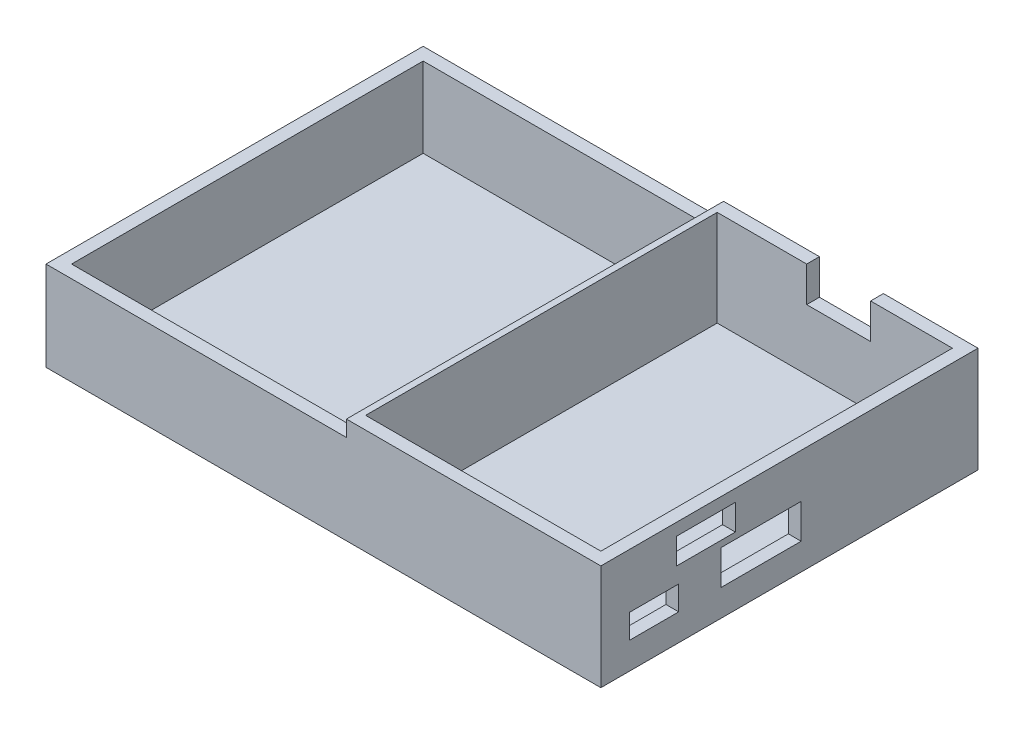
SolidWorks part; units mm, degrees
ref_plane "Front Plane" through (0, 0, 0) normal (0, 0, 1) x (1, 0, 0)
ref_plane "Top Plane" through (0, 0, 0) normal (0, 1, 0) x (1, 0, 0)
ref_plane "Right Plane" through (0, 0, 0) normal (1, 0, 0) x (0, 0, -1)
sketch "Sketch1" plane through (0, 0, 0) normal (0, 1, 0) x (1, 0, 0)
  line L1 (22.5, -27.5) -> (-22.5, -27.5)
  line L2 (22.5, -27.5) -> (22.5, 27.5)
  line L3 (22.5, 27.5) -> (-22.5, 27.5)
  line L4 (-22.5, -27.5) -> (-22.5, 27.5)
  line L5 (22.5, -27.5) -> (-22.5, 27.5) construction
  line L6 (22.5, 27.5) -> (-22.5, -27.5) construction
  line L10 (23.5, 27.5) -> (23.5, -27.5)
  line L11 (23.5, 27.5) -> (60.3, 27.5)
  line L12 (23.5, -27.5) -> (60.3, -27.5)
  line L13 (60.3, 27.5) -> (60.3, -27.5)
  line L14 (22.5, 27.5) -> (22.5, -27.5)
  line L15 (22.5, 27.5) -> (23.5, 27.5)
  line L16 (22.5, -27.5) -> (23.5, -27.5)
  line L17 (23.5, 27.5) -> (23.5, -27.5)
  line L18 (22.5, -29.5) -> (-24.5, -29.5)
  line L19 (-24.5, -29.5) -> (-24.5, 29.5)
  line L20 (22.5, 29.5) -> (-24.5, 29.5)
  line L21 (22.5, 29.5) -> (23.5, 29.5)
  line L22 (23.5, 29.5) -> (62.3, 29.5)
  line L23 (62.3, 29.5) -> (62.3, -29.5)
  line L24 (23.5, -29.5) -> (62.3, -29.5)
  line L25 (22.5, -29.5) -> (23.5, -29.5)
  line L26 (22.5, 29.5) -> (22.5, 27.5)
  line L27 (22.5, -27.5) -> (22.5, -29.5)
  line L29 (22.5, 27.5) -> (23.5, 27.5)
  line L30 (22.5, 27.5) -> (22.5, -27.5)
  line L31 (22.5, -27.5) -> (23.5, -27.5)
  line L32 (23.5, 27.5) -> (23.5, -27.5)
  point P0 (0, 0)
  point P18 (-62.1185, 18.7953)
  dimension "D1" = 55
  dimension "D2" = 45
  dimension "D3" = 1
  dimension "D4" = 2
  dimension "D5" = 86.8
  dimension "D6" = 36.8
  dimension "D7" = 59
extrude "Boss-Extrude1" add sketch "Sketch1" along normal blind 12.5 contours L27 L1 L4 L3 L26 L20 L19 L18 region at (21.7457, 0, 28.5)
extrude "Boss-Extrude2" add sketch "Sketch1<5>" along normal blind 15 contours L16 L27 L25 L24 L23 L22 L21 L26 L15 L11 L13 L12 region at (23, 0, 28.2117)
sketch "Sketch1<5>" plane through (0, 0, 0) normal (0, 1, 0) x (1, 0, 0) same geometry as "Sketch1"
extrude "Boss-Extrude3" add sketch "Sketch1<7>" along normal blind 15 contours L2 L16 L10 L15 region at (23, 0, 0)
sketch "Sketch1<7>" plane through (0, 0, 0) normal (0, 1, 0) x (1, 0, 0) same geometry as "Sketch1"
extrude "Boss-Extrude5" add sketch "Sketch1<10>" against normal blind 1.5 contours L27 L1 L4 L3 L26 L20 L19 L18 | L4 L1 L2 L3 | L13 L11 L10 L12 | L2 L16 L10 L15 | L16 L27 L25 L24 L23 L22 L21 L26 L15 L11 L13 L12 region at (21.7457, 0, 28.5) region at (0, 0, 0) region at (23, 0, 0) region at (23, 0, 28.2117) region at (41.9, 0, 0)
sketch "Sketch1<10>" plane through (0, 0, 0) normal (0, 1, 0) x (1, 0, 0) same geometry as "Sketch1"
sketch "Sketch2" plane through (62.3, 0, 0) normal (1, 0, 0) x (0, 0, -1)
  line L0 (-25, 2.6848) -> (-17.3172, 2.6848)
  line L1 (-25, 2.6848) -> (-25, 6.4701)
  line L2 (-25, 6.4701) -> (-17.3172, 6.4701)
  line L3 (-17.3172, 2.6848) -> (-17.3172, 6.4701)
  line L4 (-10.6702, 2.6801) -> (-10.6702, 8.0801)
  line L5 (-10.6702, 8.0801) -> (1.8298, 8.0801)
  line L6 (1.8298, 2.6801) -> (1.8298, 8.0801)
  line L7 (-10.6702, 2.6801) -> (1.8298, 2.6801)
  line L8 (-17.6602, 9.0683) -> (-8.4602, 9.0683)
  line L9 (-17.6602, 9.0683) -> (-17.6602, 13.1)
  line L10 (-17.6602, 13.1) -> (-8.4602, 13.1)
  line L11 (-8.4602, 9.0683) -> (-8.4602, 13.1)
  line L12 (-29.5, 15) -> (-29.5, -1.5) construction
  line L13 (29.5, 15) -> (-29.5, 15) construction
  dimension "D1" = 0.9882
  dimension "D2" = 2.5982
  dimension "D3" = 9.2
  dimension "D4" = 2.21
  dimension "D5" = 0.343
  dimension "D6" = 4.5
  dimension "D7" = 1.9
  dimension "D8" = 4.0317
extrude "Cut-Extrude1" cut sketch "Sketch2" against normal blind 10
sketch "Sketch3" plane through (0, 0, -29.5) normal (0, 0, -1) x (-1, 0, 0)
  line L0 (-22.5, 15) -> (-22.5, 12.5) construction
  line L1 (-47.5, 15) -> (-37.5, 15)
  line L2 (-47.5, 15) -> (-47.5, 9.5)
  line L3 (-47.5, 9.5) -> (-37.5, 9.5)
  line L4 (-37.5, 15) -> (-37.5, 9.5)
  line L5 (-22.5, 15) -> (-62.3, 15) construction
  dimension "D1" = 15
  dimension "D2" = 0
  dimension "D3" = 5.5
  dimension "D4" = 10
extrude "Cut-Extrude2" cut sketch "Sketch3" against normal blind 10
